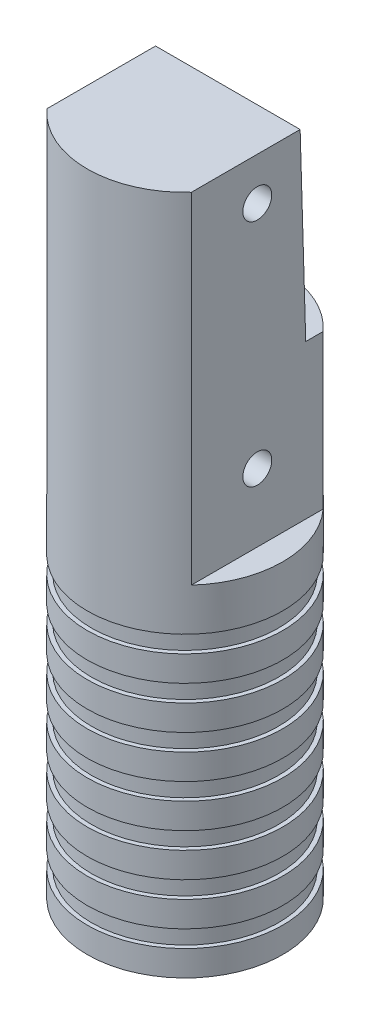
SolidWorks part; units mm, degrees
material "6061-T6 (SS)"
ref_plane "Front Plane" through (0, 0, 0) normal (0, 0, 1) x (1, 0, 0)
ref_plane "Top Plane" through (0, 0, 0) normal (0, 1, 0) x (1, 0, 0)
ref_plane "Right Plane" through (0, 0, 0) normal (1, 0, 0) x (0, 0, -1)
sketch "Sketch2" plane through (0, 0, 0) normal (0, 0, 1) x (1, 0, 0)
  line L0 (-11.5, 0) -> (11.5, 0)
  line L1 (11.5, 0) -> (11.5, -40)
  line L2 (11.5, -40) -> (0, -40)
  line L4 (0, 0) -> (0, -40)
  line L6 (-11.5, -40) -> (0, -40)
  line L7 (-11.5, 0) -> (-11.5, -40)
  point P4 (0, 0)
  dimension "D1" = 23
  dimension "D4" = 40
revolve "Revolve1" add sketch "Sketch2" angle 360 about L4 region at (-5.75, -20, 0)
sketch "Sketch3" plane through (0, 0, 0) normal (0, 0, 1) x (1, 0, 0)
  line L0 (-11.5, -40) -> (11.5, -40) construction
  line L1 (-11.5, -40) -> (11.5, -40)
  line L2 (11.5, -40) -> (11.5, -37)
  line L3 (11.5, -40) -> (11.5, 0) construction
  line L4 (11.5, -37) -> (11, -37)
  line L5 (11, -37) -> (11, -35)
  line L6 (11, -35) -> (11.5, -35)
  line L7 (11.5, -37) -> (11.5, -35)
  dimension "D1" = 2
  dimension "D2" = 0.5
  dimension "D3" = 3
revolve "Cut-Revolve1" cut sketch "Sketch3" angle 360 about L4
pattern_linear "LPattern1" count 7 spacing 5 along (0, 1, 0) of "Cut-Revolve1"
sketch "Sketch4" plane through (0, -40, 0) normal (0, -1, 0) x (1, 0, 0)
  point P0 (0, 0)
sketch "Sketch6" plane through (0, 0, 0) normal (0, 1, 0) x (1, 0, 0)
  line L0 (-8.5, 7.746) -> (-8.5, -7.746)
  line L2 (0, 0) -> (0, 11.5) construction
  line L3 (8.5, 7.746) -> (8.5, -7.746)
  line L4 (0, 0) -> (-8.5, 0) construction
  line L5 (-8.5, 1.5) -> (0, 1.5) construction
  arc A0 (8.5, 7.746) -> (-8.5, 7.746) centre (0, 0) ccw
  circle A1 centre (0, 0) radius 11.5 construction
  arc A2 (8.5, -7.746) -> (-8.5, -7.746) centre (0, 0) cw
  point P7 (-11.5, 0)
  dimension "D1" = 3
  dimension "D2" = 1.5
extrude "Boss-Extrude1" add sketch "Sketch6" along normal blind 40
hole_wizard "Ø15.0 (15) Diameter Hole1" positions "Sketch4" profile "Sketch5" hole size "Ø15.0" standard "ANSI Metric"
sketch "Sketch5" plane through (0, -40, 0) normal (1, 0, 0) x (0, 0, -1)
  line L0 (0, 0) -> (0, 44.5065)
  line L1 (0, 44.5065) -> (7.5, 40)
  line L2 (7.5, 40) -> (7.5, 0)
  line L5 (7.5, 0) -> (0, 0)
  line L10 (0, 44.5065) -> (-7.5, 40) construction
  line L11 (0, -6.35) -> (0, 107.95) construction
  dimension "Hole Dia." = 15
  dimension "Hole Depth" = 40
  dimension "Drill Angle" = 118
sketch "Sketch8" plane through (8.5, 0, 0) normal (1, 0, 0) x (0, 0, -1)
  line L2 (0, 8) -> (0, 35) construction
  line L3 (7.746, 0) -> (-7.746, 0) construction
  circle A0 centre (0, 8) radius 1.5 construction
  point P0 (0, 8)
  point P1 (0, 35)
  dimension "D1" = 3
  dimension "D2" = 8
  dimension "D3" = 27
hole_wizard "M3 Clearance Hole1" positions "Sketch8" profile "Sketch14" hole size "M3" standard "ANSI Metric" end condition through all
sketch "Sketch14" plane through (8.5, 8, 0) normal (0, 1, 0) x (0, 0, -1)
  line L0 (0, 0) -> (0, 20)
  line L1 (0, 20) -> (1.7, 20)
  line L2 (1.7, 20) -> (1.7, 0)
  line L5 (1.7, 0) -> (0, 0)
  line L11 (0, -6.35) -> (0, 107.95) construction
  dimension "Thru Hole Dia." = 3.4
  dimension "Thru Hole Depth" = 20
sketch "Sketch16" plane through (0, 0, 0) normal (1, 0, 0) x (0, 0, -1)
  line L0 (50.0175, 86.3497) -> (50.0175, 73.3497) construction
  line L1 (50.0175, -3.6503) -> (50.0175, 9.3497) construction
  line L2 (5.0377, 40) -> (5.6954, 18.0816)
  line L3 (5.6954, 18.0816) -> (11.5, 18.0816)
  line L4 (11.5, 40) -> (7.746, 40) construction
  line L5 (11.5, 40) -> (7.746, 40)
  line L6 (7.746, 40) -> (5.0377, 40)
  line L7 (11.5, -5) -> (11.5, 40) construction
  line L8 (11.5, 18.0816) -> (11.5, 40)
  circle A0 centre (0, 8) radius 1.7 construction
  circle A1 centre (0, 35) radius 1.7 construction
  circle A2 centre (0, 8) radius 1.7
  circle A3 centre (0, 35) radius 1.7
  arc A4 (50.0175, -3.6503) -> (50.0175, 86.3497) centre (50.0175, 41.3497) cw construction
  arc A5 (50.0175, 73.3497) -> (50.0175, 9.3497) centre (50.0175, 41.3497) ccw construction
  dimension "D1" = 32
  dimension "D4" = 13
  dimension "D2" = 60.1162
  dimension "D3" = 50.4189
extrude "Cut-Extrude1" cut sketch "Sketch16" against normal through all both and the other way through all
